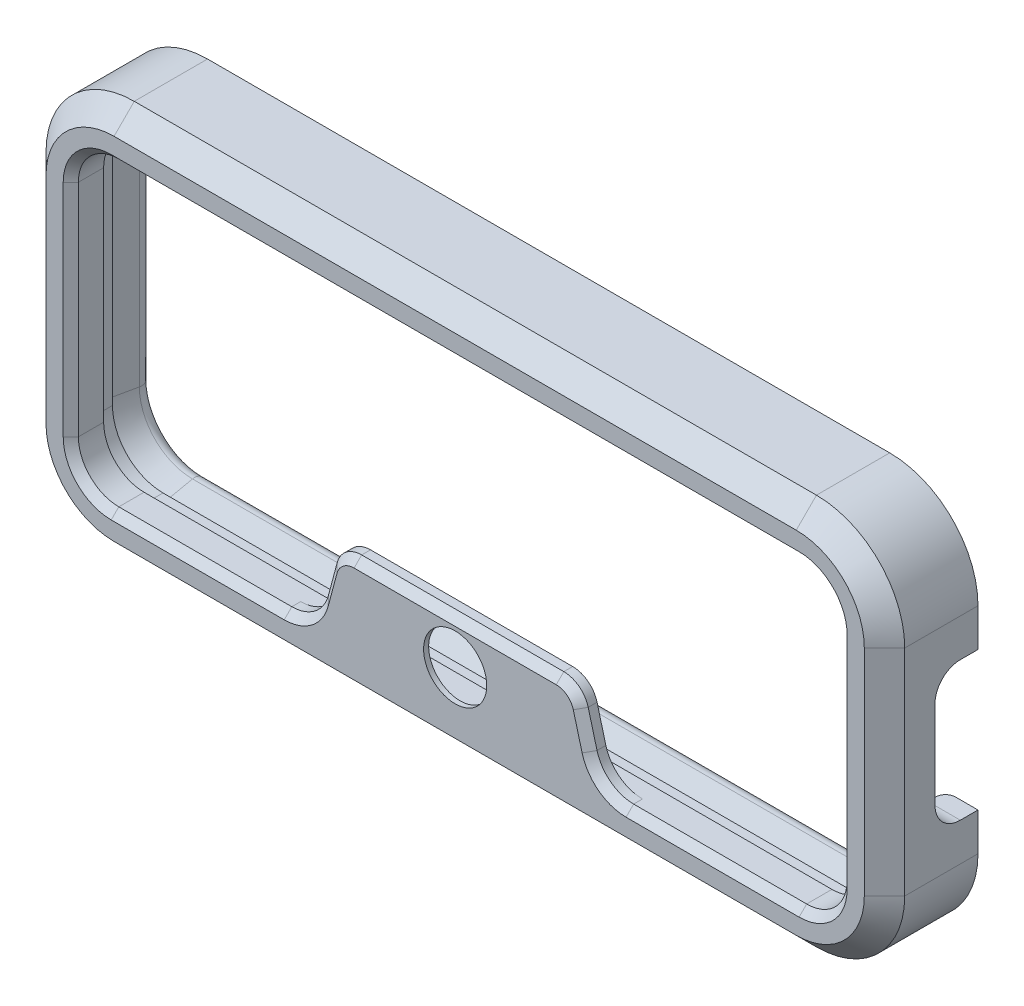
SolidWorks part; units mm, degrees
ref_plane "Ebene vorne" through (0, 0, 0) normal (0, 0, 1) x (1, 0, 0)
ref_plane "Ebene oben" through (0, 0, 0) normal (0, 1, 0) x (1, 0, 0)
ref_plane "Ebene rechts" through (0, 0, 0) normal (1, 0, 0) x (0, 0, -1)
sketch "Skizze1" plane through (0, 0, 2.3001) normal (0, 0, 1) x (1, 0, 0)
  line L0 (-27.9511, -4.5825) -> (-26.1511, -4.5825)
  line L1 (-26.1511, -4.5825) -> (-26.1511, 2.6565)
  line L2 (-26.1511, 2.6565) -> (-22.49, 2.6565)
  line L3 (-22.49, 2.6565) -> (-22.49, -4.5825)
  line L4 (-22.49, -4.5825) -> (-20.69, -4.5825)
  line L5 (-20.69, -4.5825) -> (-20.69, 2.6565)
  line L6 (-20.69, 2.6565) -> (-17.41, 2.6565)
  line L7 (-17.41, 2.6565) -> (-17.41, -4.5825)
  line L8 (-17.41, -4.5825) -> (-15.61, -4.5825)
  line L10 (-16.2652, 4.4565) -> (-27.9511, 4.4565)
  line L11 (-27.9511, 4.4565) -> (-27.9511, -4.5825)
  line L24 (-11.695, 4.4565) -> (-5.069, 4.4565)
  line L25 (-5.069, 4.4565) -> (-5.069, -4.5825)
  line L26 (-5.069, -4.5825) -> (-9.095, -4.5825)
  line L27 (-9.095, -4.5825) -> (-11.695, -4.1241)
  line L28 (-11.695, -4.1241) -> (-11.695, 0.2038)
  line L29 (-11.695, 0.2038) -> (-9.095, 0.9005)
  line L31 (-7.355, -0.8995) -> (-9.895, -0.8995)
  line L32 (-9.895, -0.8995) -> (-9.895, -2.7825)
  line L33 (-9.895, -2.7825) -> (-6.869, -2.7825)
  line L34 (-6.869, -2.7825) -> (-6.869, 2.6565)
  line L35 (-6.869, 2.6565) -> (-11.695, 2.6565)
  line L36 (-11.695, 2.6565) -> (-11.695, 4.4565)
  line L50 (1.259, 8.3935) -> (1.259, 4.4565)
  line L51 (1.259, 4.4565) -> (-1.154, 4.4565)
  line L52 (-1.154, 4.4565) -> (-1.154, 2.6565)
  line L53 (-1.154, 2.6565) -> (1.259, 2.6565)
  line L54 (1.259, 2.6565) -> (1.259, -4.5825)
  line L55 (1.259, -4.5825) -> (5.472, -4.5825)
  line L56 (5.472, -4.5825) -> (5.472, -2.7825)
  line L57 (5.472, -2.7825) -> (3.059, -2.7825)
  line L58 (3.059, -2.7825) -> (3.059, 2.6565)
  line L59 (3.059, 2.6565) -> (5.472, 2.6565)
  line L60 (5.472, 2.6565) -> (5.472, 4.4565)
  line L61 (5.472, 4.4565) -> (3.059, 4.4565)
  line L62 (3.059, 4.4565) -> (3.059, 8.3935)
  line L63 (3.059, 8.3935) -> (1.259, 8.3935)
  line L64 (-16.01, 0.6435) -> (-16.01, 1.6435) construction
  line L65 (-27.5511, 4.0565) -> (-27.5511, 3.0565) construction
  line L66 (-26.5511, -1.7695) -> (-26.5511, -0.7695) construction
  line L67 (-22.09, 1.6435) -> (-22.09, 0.6435) construction
  line L68 (-21.09, 0.6435) -> (-21.09, 1.6435) construction
  line L69 (-20.312, 3.0565) -> (-19.312, 3.0565) construction
  line L70 (-15.61, 2.6565) -> (-16.2652, 4.4565)
  line L71 (-24.138, 4.0565) -> (-25.138, 4.0565) construction
  line L72 (-27.5511, -4.1825) -> (-26.5511, -4.1825) construction
  line L73 (-17.01, 1.6435) -> (-17.01, 0.6435) construction
  line L74 (19.928, 8.2665) -> (19.928, -4.5825)
  line L75 (19.928, -4.5825) -> (21.728, -4.5825)
  line L76 (21.728, -4.5825) -> (21.728, 2.6565)
  line L77 (21.728, 2.6565) -> (25.8971, 2.6565)
  line L78 (25.8971, 2.6565) -> (25.8971, -4.5825)
  line L79 (25.8971, -4.5825) -> (27.6971, -4.5825)
  line L80 (27.6971, -4.5825) -> (27.6971, 2.6565)
  line L83 (27.0419, 4.4565) -> (21.728, 4.4565)
  line L84 (21.728, 4.4565) -> (21.728, 8.2665)
  line L85 (21.728, 8.2665) -> (19.928, 8.2665)
  line L86 (16.013, 2.6565) -> (12.057, 2.6565)
  line L87 (12.057, 2.6565) -> (11.187, 1.7865)
  line L88 (11.187, 1.7865) -> (11.187, -1.9125)
  line L89 (11.187, -1.9125) -> (12.057, -2.7825)
  line L90 (12.057, -2.7825) -> (16.013, -2.7825)
  line L91 (16.013, -2.7825) -> (16.013, -4.5825)
  line L92 (16.013, -4.5825) -> (11.155, -4.5825)
  line L93 (11.155, -4.5825) -> (9.387, -3.099)
  line L94 (9.387, -3.099) -> (9.387, 2.973)
  line L95 (9.387, 2.973) -> (11.155, 4.4565)
  line L96 (11.155, 4.4565) -> (16.013, 4.4565)
  line L97 (16.013, 4.4565) -> (16.013, 2.6565)
  line L98 (-0.754, 4.0565) -> (-0.754, 3.0565) construction
  line L99 (0.246, 4.0565) -> (-0.754, 4.0565) construction
  line L100 (1.659, 5.1995) -> (1.659, 4.1995) construction
  line L101 (2.659, 7.9935) -> (1.659, 7.9935) construction
  line L102 (2.659, 6.9935) -> (2.659, 7.9935) construction
  line L103 (5.072, 3.0565) -> (5.072, 4.0565) construction
  line L104 (4.072, 3.0565) -> (5.072, 3.0565) construction
  line L105 (2.659, 1.4055) -> (2.659, 2.4055) construction
  line L106 (5.072, -4.1825) -> (5.072, -3.1825) construction
  line L107 (5.072, -3.1825) -> (4.072, -3.1825) construction
  line L108 (1.659, -4.1825) -> (2.659, -4.1825) construction
  line L109 (9.787, 0.3735) -> (9.787, -0.6265) construction
  line L110 (10.787, -0.6265) -> (10.787, 0.3735) construction
  line L111 (-11.295, 4.0565) -> (-11.295, 3.0565) construction
  line L112 (-10.295, 4.0565) -> (-11.295, 4.0565) construction
  line L113 (14.613, 3.0565) -> (15.613, 3.0565) construction
  line L114 (15.613, 3.0565) -> (15.613, 4.0565) construction
  line L115 (13.2, 4.0565) -> (12.2, 4.0565) construction
  line L116 (12.2, -4.1825) -> (13.2, -4.1825) construction
  line L117 (20.328, -0.2615) -> (20.328, -1.2615) construction
  line L118 (21.328, -1.2615) -> (21.328, -0.2615) construction
  line L119 (22.741, 3.0565) -> (23.741, 3.0565) construction
  line L120 (26.2971, 1.7705) -> (26.2971, 0.7705) construction
  line L121 (27.2971, 0.7705) -> (27.2971, 1.7705) construction
  line L122 (23.741, 4.0565) -> (22.741, 4.0565) construction
  line L123 (21.328, 7.8665) -> (20.328, 7.8665) construction
  line L124 (21.328, 6.8665) -> (21.328, 7.8665) construction
  line L125 (27.6971, 2.6565) -> (27.0419, 4.4565)
  line L126 (20.328, -4.1825) -> (21.328, -4.1825) construction
  line L127 (-15.61, -4.5825) -> (-15.61, 2.6565)
  line L129 (-11.295, 3.0565) -> (-10.295, 3.0565) construction
  line L130 (-11.295, -0.1345) -> (-11.295, -1.1345) construction
  line L131 (-8.882, -4.1825) -> (-7.882, -4.1825) construction
  line L132 (-5.469, 3.0565) -> (-5.469, 4.0565) construction
  line L134 (-6.469, 1.6435) -> (-6.469, 0.6435) construction
  line L135 (-7.882, -3.1825) -> (-8.882, -3.1825) construction
  line L136 (-10.295, -1.1345) -> (-10.295, -0.1345) construction
  line L137 (-9.095, 0.9005) -> (-7.355, 0.9005)
  line L138 (-7.355, 0.9005) -> (-7.355, -0.8995)
  line L140 (-7.755, 0.5005) -> (-8.755, 0.5005) construction
  line L141 (-4.469, 4.8565) -> (-12.095, 4.8565)
  line L142 (-4.469, 4.8565) -> (-4.469, -5.1825)
  line L143 (-4.469, -5.1825) -> (-12.095, -5.1825)
  line L144 (-12.095, 4.8565) -> (-12.095, -5.1825)
  line L145 (-7.755, -0.4995) -> (-7.755, 0.5005) construction
  line L146 (-8.755, -0.4995) -> (-7.755, -0.4995) construction
  line L147 (-15.9151, 4.9565) -> (-28.4511, 4.9565)
  line L148 (-28.4511, 4.9565) -> (-28.4511, -5.0825)
  line L149 (-28.4511, -5.0825) -> (-25.6511, -5.0825)
  line L150 (-25.6511, -5.0825) -> (-25.6511, 2.1565)
  line L151 (-25.6511, 2.1565) -> (-22.99, 2.1565)
  line L152 (-22.99, 2.1565) -> (-22.99, -5.0825)
  line L153 (-22.99, -5.0825) -> (-20.19, -5.0825)
  line L154 (-20.19, -5.0825) -> (-20.19, 2.1565)
  line L155 (-20.19, 2.1565) -> (-17.91, 2.1565)
  line L156 (-17.91, 2.1565) -> (-17.91, -5.0825)
  line L157 (-17.91, -5.0825) -> (-15.11, -5.0825)
  line L158 (-15.11, -5.0825) -> (-15.11, 2.7447)
  line L159 (-15.11, 2.7447) -> (-15.9151, 4.9565)
  line L160 (5.972, 4.9565) -> (3.559, 4.9565)
  line L161 (3.559, 4.9565) -> (3.559, 8.8935)
  line L162 (3.559, 8.8935) -> (0.759, 8.8935)
  line L163 (0.759, 8.8935) -> (0.759, 4.9565)
  line L164 (0.759, 4.9565) -> (-1.654, 4.9565)
  line L165 (-1.654, 4.9565) -> (-1.654, 2.1565)
  line L166 (-1.654, 2.1565) -> (0.759, 2.1565)
  line L167 (0.759, 2.1565) -> (0.759, -5.0825)
  line L168 (0.759, -5.0825) -> (5.972, -5.0825)
  line L169 (5.972, -5.0825) -> (5.972, -2.2825)
  line L170 (5.972, -2.2825) -> (3.559, -2.2825)
  line L171 (3.559, -2.2825) -> (3.559, 2.1565)
  line L172 (3.559, 2.1565) -> (5.972, 2.1565)
  line L173 (5.972, 2.1565) -> (5.972, 4.9565)
  line L174 (10.973, 4.9565) -> (16.513, 4.9565)
  line L175 (16.513, 4.9565) -> (16.513, 2.1565)
  line L176 (16.513, 2.1565) -> (12.2641, 2.1565)
  line L177 (12.2641, 2.1565) -> (11.687, 1.5794)
  line L178 (11.687, 1.5794) -> (11.687, -1.7054)
  line L179 (11.687, -1.7054) -> (12.2641, -2.2825)
  line L180 (12.2641, -2.2825) -> (16.513, -2.2825)
  line L181 (16.513, -2.2825) -> (16.513, -5.0825)
  line L182 (16.513, -5.0825) -> (10.973, -5.0825)
  line L183 (10.973, -5.0825) -> (8.887, -3.3322)
  line L184 (8.887, -3.3322) -> (8.887, 3.2062)
  line L185 (8.887, 3.2062) -> (10.973, 4.9565)
  line L186 (27.322, 4.8565) -> (22.128, 4.8565)
  line L187 (22.128, 4.8565) -> (22.128, 8.6665)
  line L188 (22.128, 8.6665) -> (19.528, 8.6665)
  line L189 (19.528, 8.6665) -> (19.528, -4.9825)
  line L190 (19.528, -4.9825) -> (22.128, -4.9825)
  line L191 (22.128, -4.9825) -> (22.128, 2.2565)
  line L192 (22.128, 2.2565) -> (25.4971, 2.2565)
  line L193 (25.4971, 2.2565) -> (25.4971, -4.9825)
  line L194 (25.4971, -4.9825) -> (28.0971, -4.9825)
  line L195 (28.0971, -4.9825) -> (28.0971, 2.727)
  line L196 (28.0971, 2.727) -> (27.322, 4.8565)
  dimension "D1" = 0.4
  dimension "D2" = 0.4
  dimension "D3" = 0.4
  dimension "D4" = 0.4
  dimension "D5" = 0.4
  dimension "D7" = 0.4
  dimension "D8" = 0.4
  dimension "D9" = 0.4
  dimension "D10" = 0.4
  dimension "D11" = 0.4
  dimension "D12" = 0.4
  dimension "D13" = 0.4
  dimension "D14" = 0.4
  dimension "D15" = 0.4
  dimension "D16" = 0.4
  dimension "D17" = 0.4
  dimension "D18" = 0.4
  dimension "D19" = 0.4
  dimension "D20" = 0.4
  dimension "D21" = 0.4
  dimension "D22" = 0.4
  dimension "D23" = 0.4
  dimension "D24" = 0.4
  dimension "D25" = 0.4
  dimension "D26" = 0.4
  dimension "D27" = 130
  dimension "D28" = 135
  dimension "D29" = 0.4
  dimension "D30" = 0.4
  dimension "D31" = 0.4
  dimension "D32" = 0.4
  dimension "D33" = 0.4
  dimension "D34" = 0.4
  dimension "D35" = 0.4
  dimension "D36" = 0.4
  dimension "D37" = 0.4
  dimension "D38" = 0.4
  dimension "D39" = 20
  dimension "D40" = 0.4
  dimension "D6" = 0.4
  dimension "D41" = 200
  dimension "D42" = 0.4
  dimension "D43" = 0.4
  dimension "D44" = 0.4
  dimension "D45" = 0.4
  dimension "D46" = 0.4
  dimension "D47" = 0.4
  dimension "D48" = 0.4
  dimension "D49" = 0.4
  dimension "D50" = 0.4
  dimension "D51" = 105
  dimension "D52" = 0.4
  dimension "D53" = 0.4
  dimension "D54" = 0.4
  dimension "D55" = 2.6
  dimension "D56" = 0.4
  dimension "D58" = 0.6
  dimension "D59" = 0.4
  dimension "D57" = 10
  dimension "D64" = 2.6
  dimension "D65" = 0.6
  dimension "D60" = 0.5
  dimension "D61" = 0.5
  dimension "D62" = 0.5
  dimension "D63" = 0.4
extrude "Aufsatz-Linear austragen1" add sketch "Skizze1" along normal blind 1.5
sketch "Skizze2" plane through (0, 0, 3.8001) normal (0, 0, 1) x (1, 0, 0)
  line L0 (30.9874, 8.5) -> (30.9874, -8.5) construction
  line L1 (27.0001, -12.4873) -> (-27.0001, -12.4873) construction
  line L2 (-30.9874, -8.5) -> (-30.9874, 8.5) construction
  line L3 (-27.0001, 12.4873) -> (27.0001, 12.4873) construction
  line L4 (30.9874, 8.5) -> (30.9874, -8.5) construction
  line L5 (27.0001, -12.4873) -> (-27.0001, -12.4873) construction
  line L6 (-30.9874, -8.5) -> (-30.9874, 8.5) construction
  line L7 (-27.0001, 12.4873) -> (27.0001, 12.4873) construction
  line L8 (-27.0001, 15.4873) -> (27.0001, 15.4873)
  line L9 (33.9874, 8.5) -> (33.9874, -8.5)
  line L10 (27.0001, -15.4873) -> (-27.0001, -15.4873)
  line L11 (-33.9874, -8.5) -> (-33.9874, 8.5)
  arc A0 (30.9874, 8.5) -> (27.0001, 12.4873) centre (27.0001, 8.5) ccw construction
  arc A1 (27.0001, -12.4873) -> (30.9874, -8.5) centre (27.0001, -8.5) ccw construction
  arc A2 (-30.9874, -8.5) -> (-27.0001, -12.4873) centre (-27.0001, -8.5) ccw construction
  arc A3 (-27.0001, 12.4873) -> (-30.9874, 8.5) centre (-27.0001, 8.5) ccw construction
  arc A4 (30.9874, 8.5) -> (27.0001, 12.4873) centre (27.0001, 8.5) ccw construction
  arc A5 (27.0001, -12.4873) -> (30.9874, -8.5) centre (27.0001, -8.5) ccw construction
  arc A6 (-30.9874, -8.5) -> (-27.0001, -12.4873) centre (-27.0001, -8.5) ccw construction
  arc A7 (-27.0001, 12.4873) -> (-30.9874, 8.5) centre (-27.0001, 8.5) ccw construction
  circle A8 centre (0, -9.017) radius 2.5
  arc A9 (0.7218, -9.017) -> (-0.7218, -9.017) centre (0, -9.017) ccw construction
  arc A10 (0.7218, -9.017) -> (-0.7218, -9.017) centre (0, -9.017) ccw construction
  arc A11 (33.9874, 8.5) -> (27.0001, 15.4873) centre (27.0001, 8.5) ccw
  arc A12 (27.0001, -15.4873) -> (33.9874, -8.5) centre (27.0001, -8.5) ccw
  arc A13 (-33.9874, -8.5) -> (-27.0001, -15.4873) centre (-27.0001, -8.5) ccw
  arc A14 (-27.0001, 15.4873) -> (-33.9874, 8.5) centre (-27.0001, 8.5) ccw
  dimension "D1" = 5
  dimension "D2" = 3
extrude "Aufsatz-Linear austragen2" add sketch "Skizze2" along normal blind 0.4
sketch "Skizze3" plane through (0, 0, 3.8001) normal (0, 0, -1) x (-1, 0, 0)
  line L12 (-27.225, 11.925) -> (27.225, 11.925)
  line L13 (-27.225, -12.725) -> (27.225, -12.725)
  line L14 (-31.225, -8.725) -> (-31.225, 8.725)
  line L15 (-27.225, 12.725) -> (27.225, 12.725)
  line L16 (31.225, -8.725) -> (31.225, 8.725)
  line L17 (-31.225, -12.725) -> (31.225, 12.725) construction
  line L18 (-31.225, 12.725) -> (31.225, -12.725) construction
  line L19 (30.425, -8.725) -> (30.425, 8.725)
  line L20 (-27.225, -11.925) -> (27.225, -11.925)
  line L21 (-30.425, -8.725) -> (-30.425, 8.725)
  arc A12 (27.225, 12.725) -> (31.225, 8.725) centre (27.225, 8.725) cw
  arc A13 (27.225, -12.725) -> (31.225, -8.725) centre (27.225, -8.725) ccw
  arc A14 (-31.225, -8.725) -> (-27.225, -12.725) centre (-27.225, -8.725) ccw
  arc A15 (-31.225, 8.725) -> (-27.225, 12.725) centre (-27.225, 8.725) cw
  arc A16 (27.225, 11.925) -> (30.425, 8.725) centre (27.225, 8.725) cw
  arc A17 (27.225, -11.925) -> (30.425, -8.725) centre (27.225, -8.725) ccw
  arc A18 (-30.425, -8.725) -> (-27.225, -11.925) centre (-27.225, -8.725) ccw
  arc A19 (-30.425, 8.725) -> (-27.225, 11.925) centre (-27.225, 8.725) cw
  point P0 (0, 0)
  dimension "D3" = 4
  dimension "D1" = 62.45
  dimension "D2" = 25.45
  dimension "D4" = 0.8
extrude "Aufsatz-Linear austragen3" add sketch "Skizze3" along normal blind 2.2
sketch "Skizze10" plane through (0, 0, 3.8001) normal (0, 0, -1) x (-1, 0, 0)
  line L0 (27.225, 12.725) -> (-27.225, 12.725) construction
  line L1 (27.225, 12.725) -> (-27.225, 12.725)
  line L4 (27.0001, 15.4873) -> (-27.0001, 15.4873)
  line L5 (-33.9874, 8.5) -> (-33.9874, -8.5)
  line L6 (-27.0001, -15.4873) -> (27.0001, -15.4873)
  line L7 (33.9874, -8.5) -> (33.9874, 8.5)
  line L8 (27.0001, 15.4873) -> (-27.0001, 15.4873)
  line L9 (-33.9874, 8.5) -> (-33.9874, -8.5)
  line L10 (-27.0001, -15.4873) -> (27.0001, -15.4873)
  line L11 (33.9874, -8.5) -> (33.9874, 8.5)
  line L14 (31.225, -8.725) -> (31.225, 8.725)
  line L15 (31.225, -8.725) -> (31.225, 8.725)
  line L16 (-27.225, -12.725) -> (27.225, -12.725)
  line L17 (-27.225, -12.725) -> (27.225, -12.725)
  line L22 (-31.225, 8.725) -> (-31.225, -8.725)
  line L23 (-31.225, 8.725) -> (-31.225, -8.725)
  line L24 (27.225, 12.725) -> (-27.225, 12.725)
  line L25 (27.225, 12.725) -> (-27.225, 12.725)
  arc A1 (27.225, -12.725) -> (31.225, -8.725) centre (27.225, -8.725) ccw
  arc A4 (33.9874, 8.5) -> (27.0001, 15.4873) centre (27.0001, 8.5) ccw
  arc A5 (-27.0001, 15.4873) -> (-33.9874, 8.5) centre (-27.0001, 8.5) ccw
  arc A6 (-33.9874, -8.5) -> (-27.0001, -15.4873) centre (-27.0001, -8.5) ccw
  arc A7 (27.0001, -15.4873) -> (33.9874, -8.5) centre (27.0001, -8.5) ccw
  arc A8 (33.9874, 8.5) -> (27.0001, 15.4873) centre (27.0001, 8.5) ccw
  arc A9 (-27.0001, 15.4873) -> (-33.9874, 8.5) centre (-27.0001, 8.5) ccw
  arc A10 (-33.9874, -8.5) -> (-27.0001, -15.4873) centre (-27.0001, -8.5) ccw
  arc A11 (27.0001, -15.4873) -> (33.9874, -8.5) centre (27.0001, -8.5) ccw
  arc A15 (27.225, -12.725) -> (31.225, -8.725) centre (27.225, -8.725) ccw
  arc A20 (-31.225, -8.725) -> (-27.225, -12.725) centre (-27.225, -8.725) ccw
  arc A21 (-31.225, -8.725) -> (-27.225, -12.725) centre (-27.225, -8.725) ccw
  arc A22 (-27.225, 12.725) -> (-31.225, 8.725) centre (-27.225, 8.725) ccw
  arc A23 (-27.225, 12.725) -> (-31.225, 8.725) centre (-27.225, 8.725) ccw
  arc A24 (31.225, 8.725) -> (27.225, 12.725) centre (27.225, 8.725) ccw
  arc A25 (31.225, 8.725) -> (27.225, 12.725) centre (27.225, 8.725) ccw
  dimension "D1" = 0
  dimension "D2" = 0
extrude "Aufsatz-Linear austragen14" add sketch "Skizze10" along normal blind 7 contours A8 L8 A9 L9 A10 L10 A11 L11 | L15 A25 L25 A23 L23 A21 L17 A15
sketch "Skizze11" plane through (0, 0, 0) normal (1, 0, 0) x (0, 0, -1)
  line L0 (3.1999, 12.725) -> (-1.6001, 12.725) construction
  line L1 (3.1999, 12.725) -> (-0.1001, 12.725)
  line L2 (-0.1001, 12.725) -> (3.1999, 12.725)
  line L3 (3.1999, 12.725) -> (-0.1001, 13.4264)
  line L4 (-0.1001, 13.4264) -> (-0.1001, 12.725)
  line L5 (-0.1001, 13.4264) -> (3.1999, 12.725)
  line L6 (3.1999, 12.725) -> (-1.6001, 12.725)
  dimension "D1" = 12
  dimension "D2" = 1.5
sketch "Skizze12" plane through (0, 0, -3.1999) normal (0, 0, -1) x (-1, 0, 0)
  line L4 (31.225, -8.725) -> (31.225, 8.725)
  line L16 (31.225, -8.725) -> (31.225, 8.725)
  line L20 (-27.225, -12.725) -> (27.225, -12.725)
  line L22 (-27.225, -12.725) -> (27.225, -12.725)
  line L24 (-31.225, 8.725) -> (-31.225, -8.725)
  line L25 (-31.225, 8.725) -> (-31.225, -8.725)
  line L26 (27.225, 12.725) -> (-27.225, 12.725)
  line L27 (27.225, 12.725) -> (-27.225, 12.725)
  arc A4 (27.225, -12.725) -> (31.225, -8.725) centre (27.225, -8.725) ccw
  arc A16 (27.225, -12.725) -> (31.225, -8.725) centre (27.225, -8.725) ccw
  arc A20 (-31.225, -8.725) -> (-27.225, -12.725) centre (-27.225, -8.725) ccw
  arc A22 (-31.225, -8.725) -> (-27.225, -12.725) centre (-27.225, -8.725) ccw
  arc A24 (-27.225, 12.725) -> (-31.225, 8.725) centre (-27.225, 8.725) ccw
  arc A25 (-27.225, 12.725) -> (-31.225, 8.725) centre (-27.225, 8.725) ccw
  arc A26 (31.225, 8.725) -> (27.225, 12.725) centre (27.225, 8.725) ccw
  arc A27 (31.225, 8.725) -> (27.225, 12.725) centre (27.225, 8.725) ccw
  dimension "D1" = 0
sketch "Skizze14" plane through (0, 0, 3.8001) normal (0, 0, -1) x (-1, 0, 0)
  line L4 (27.225, 11.925) -> (-27.225, 11.925)
  line L5 (-30.425, 8.725) -> (-30.425, -8.725)
  line L6 (-27.225, -11.925) -> (27.225, -11.925)
  line L7 (30.425, -8.725) -> (30.425, 8.725)
  line L8 (27.225, 11.925) -> (-27.225, 11.925)
  line L9 (-30.425, 8.725) -> (-30.425, -8.725)
  line L10 (-27.225, -11.925) -> (27.225, -11.925)
  line L11 (30.425, -8.725) -> (30.425, 8.725)
  line L12 (4.469, -5.1825) -> (12.095, -5.1825)
  line L13 (4.469, 4.8565) -> (4.469, -5.1825)
  line L14 (12.095, 4.8565) -> (4.469, 4.8565)
  line L15 (12.095, -5.1825) -> (12.095, 4.8565)
  line L16 (4.469, -5.1825) -> (12.095, -5.1825)
  line L17 (4.469, 4.8565) -> (4.469, -5.1825)
  line L18 (12.095, 4.8565) -> (4.469, 4.8565)
  line L19 (12.095, -5.1825) -> (12.095, 4.8565)
  line L21 (15.9151, 4.9565) -> (15.11, 2.7447)
  line L22 (28.4511, 4.9565) -> (15.9151, 4.9565)
  line L23 (28.4511, -5.0825) -> (28.4511, 4.9565)
  line L24 (25.6511, -5.0825) -> (28.4511, -5.0825)
  line L25 (25.6511, 2.1565) -> (25.6511, -5.0825)
  line L26 (22.99, 2.1565) -> (25.6511, 2.1565)
  line L27 (22.99, -5.0825) -> (22.99, 2.1565)
  line L28 (20.19, -5.0825) -> (22.99, -5.0825)
  line L29 (20.19, 2.1565) -> (20.19, -5.0825)
  line L30 (17.91, 2.1565) -> (20.19, 2.1565)
  line L31 (17.91, -5.0825) -> (17.91, 2.1565)
  line L32 (15.11, -5.0825) -> (17.91, -5.0825)
  line L33 (15.11, 2.7447) -> (15.11, -5.0825)
  line L34 (15.9151, 4.9565) -> (15.11, 2.7447)
  line L35 (28.4511, 4.9565) -> (15.9151, 4.9565)
  line L36 (28.4511, -5.0825) -> (28.4511, 4.9565)
  line L37 (25.6511, -5.0825) -> (28.4511, -5.0825)
  line L38 (25.6511, 2.1565) -> (25.6511, -5.0825)
  line L39 (22.99, 2.1565) -> (25.6511, 2.1565)
  line L40 (22.99, -5.0825) -> (22.99, 2.1565)
  line L41 (20.19, -5.0825) -> (22.99, -5.0825)
  line L42 (20.19, 2.1565) -> (20.19, -5.0825)
  line L43 (17.91, 2.1565) -> (20.19, 2.1565)
  line L44 (17.91, -5.0825) -> (17.91, 2.1565)
  line L45 (15.11, -5.0825) -> (17.91, -5.0825)
  line L46 (15.11, 2.7447) -> (15.11, -5.0825)
  line L53 (-27.322, 4.8565) -> (-28.0971, 2.727)
  line L54 (-8.887, 3.2062) -> (-10.973, 4.9565)
  line L55 (-8.887, -3.3322) -> (-8.887, 3.2062)
  line L56 (-5.972, 4.9565) -> (-5.972, 2.1565)
  line L57 (-3.559, 4.9565) -> (-5.972, 4.9565)
  line L58 (-3.559, 8.8935) -> (-3.559, 4.9565)
  line L59 (-0.759, 8.8935) -> (-3.559, 8.8935)
  line L60 (-0.759, 4.9565) -> (-0.759, 8.8935)
  line L61 (1.654, 4.9565) -> (-0.759, 4.9565)
  line L62 (1.654, 2.1565) -> (1.654, 4.9565)
  line L63 (-0.759, 2.1565) -> (1.654, 2.1565)
  line L64 (-0.759, -5.0825) -> (-0.759, 2.1565)
  line L65 (-5.972, -5.0825) -> (-0.759, -5.0825)
  line L66 (-5.972, -2.2825) -> (-5.972, -5.0825)
  line L67 (-3.559, -2.2825) -> (-5.972, -2.2825)
  line L68 (-3.559, 2.1565) -> (-3.559, -2.2825)
  line L69 (-5.972, 2.1565) -> (-3.559, 2.1565)
  line L70 (-5.972, 4.9565) -> (-5.972, 2.1565)
  line L71 (-3.559, 4.9565) -> (-5.972, 4.9565)
  line L72 (-3.559, 8.8935) -> (-3.559, 4.9565)
  line L73 (-0.759, 8.8935) -> (-3.559, 8.8935)
  line L74 (-0.759, 4.9565) -> (-0.759, 8.8935)
  line L75 (1.654, 4.9565) -> (-0.759, 4.9565)
  line L76 (1.654, 2.1565) -> (1.654, 4.9565)
  line L77 (-0.759, 2.1565) -> (1.654, 2.1565)
  line L78 (-0.759, -5.0825) -> (-0.759, 2.1565)
  line L79 (-5.972, -5.0825) -> (-0.759, -5.0825)
  line L80 (-5.972, -2.2825) -> (-5.972, -5.0825)
  line L81 (-3.559, -2.2825) -> (-5.972, -2.2825)
  line L82 (-3.559, 2.1565) -> (-3.559, -2.2825)
  line L83 (-5.972, 2.1565) -> (-3.559, 2.1565)
  line L84 (-10.973, -5.0825) -> (-8.887, -3.3322)
  line L85 (-16.513, -5.0825) -> (-10.973, -5.0825)
  line L86 (-16.513, -2.2825) -> (-16.513, -5.0825)
  line L87 (-12.2641, -2.2825) -> (-16.513, -2.2825)
  line L88 (-11.687, -1.7054) -> (-12.2641, -2.2825)
  line L89 (-11.687, 1.5794) -> (-11.687, -1.7054)
  line L90 (-12.2641, 2.1565) -> (-11.687, 1.5794)
  line L91 (-16.513, 2.1565) -> (-12.2641, 2.1565)
  line L92 (-16.513, 4.9565) -> (-16.513, 2.1565)
  line L93 (-10.973, 4.9565) -> (-16.513, 4.9565)
  line L94 (-8.887, 3.2062) -> (-10.973, 4.9565)
  line L95 (-8.887, -3.3322) -> (-8.887, 3.2062)
  line L96 (-10.973, -5.0825) -> (-8.887, -3.3322)
  line L97 (-16.513, -5.0825) -> (-10.973, -5.0825)
  line L98 (-16.513, -2.2825) -> (-16.513, -5.0825)
  line L99 (-12.2641, -2.2825) -> (-16.513, -2.2825)
  line L100 (-11.687, -1.7054) -> (-12.2641, -2.2825)
  line L101 (-11.687, 1.5794) -> (-11.687, -1.7054)
  line L102 (-12.2641, 2.1565) -> (-11.687, 1.5794)
  line L103 (-16.513, 2.1565) -> (-12.2641, 2.1565)
  line L104 (-16.513, 4.9565) -> (-16.513, 2.1565)
  line L105 (-10.973, 4.9565) -> (-16.513, 4.9565)
  line L106 (-22.128, 4.8565) -> (-27.322, 4.8565)
  line L107 (-22.128, 8.6665) -> (-22.128, 4.8565)
  line L108 (-19.528, 8.6665) -> (-22.128, 8.6665)
  line L109 (-19.528, -4.9825) -> (-19.528, 8.6665)
  line L110 (-22.128, -4.9825) -> (-19.528, -4.9825)
  line L111 (-22.128, 2.2565) -> (-22.128, -4.9825)
  line L112 (-25.4971, 2.2565) -> (-22.128, 2.2565)
  line L113 (-25.4971, -4.9825) -> (-25.4971, 2.2565)
  line L114 (-28.0971, -4.9825) -> (-25.4971, -4.9825)
  line L115 (-28.0971, 2.727) -> (-28.0971, -4.9825)
  line L116 (-27.322, 4.8565) -> (-28.0971, 2.727)
  line L117 (-22.128, 4.8565) -> (-27.322, 4.8565)
  line L118 (-22.128, 8.6665) -> (-22.128, 4.8565)
  line L119 (-19.528, 8.6665) -> (-22.128, 8.6665)
  line L120 (-19.528, -4.9825) -> (-19.528, 8.6665)
  line L121 (-22.128, -4.9825) -> (-19.528, -4.9825)
  line L122 (-22.128, 2.2565) -> (-22.128, -4.9825)
  line L123 (-25.4971, 2.2565) -> (-22.128, 2.2565)
  line L124 (-25.4971, -4.9825) -> (-25.4971, 2.2565)
  line L125 (-28.0971, -4.9825) -> (-25.4971, -4.9825)
  line L126 (-28.0971, 2.727) -> (-28.0971, -4.9825)
  circle A1 centre (0, -9.017) radius 2.5
  circle A2 centre (0, -9.017) radius 2.5
  arc A4 (30.425, 8.725) -> (27.225, 11.925) centre (27.225, 8.725) ccw
  arc A5 (-27.225, 11.925) -> (-30.425, 8.725) centre (-27.225, 8.725) ccw
  arc A6 (-30.425, -8.725) -> (-27.225, -11.925) centre (-27.225, -8.725) ccw
  arc A7 (27.225, -11.925) -> (30.425, -8.725) centre (27.225, -8.725) ccw
  arc A8 (30.425, 8.725) -> (27.225, 11.925) centre (27.225, 8.725) ccw
  arc A9 (-27.225, 11.925) -> (-30.425, 8.725) centre (-27.225, 8.725) ccw
  arc A10 (-30.425, -8.725) -> (-27.225, -11.925) centre (-27.225, -8.725) ccw
  arc A11 (27.225, -11.925) -> (30.425, -8.725) centre (27.225, -8.725) ccw
  dimension "D1" = 0
  dimension "D2" = 0
  dimension "D3" = 0
  dimension "D4" = 0
  dimension "D5" = 0
  dimension "D6" = 0
  dimension "D7" = 0
extrude "Aufsatz-Linear austragen15" add sketch "Skizze14" along normal blind 0.9
sweep "Schnitt-Austragung1" cut profiles "Skizze11" path "Skizze12"
fillet "Verrundung1" radius 0.8 9 edges at (-30.0534, -11.5534, -3.1999) (0, -12.725, -3.1999) (30.0534, -11.5534, -3.1999) (31.225, 0, -3.1999) (30.0534, 11.5534, -3.1999) (13.6125, 12.725, -3.1999) (-13.6125, 12.725, -3.1999) (-30.0534, 11.5534, -3.1999) (-31.225, 0, -3.1999)
sketch "Skizze13" plane through (33.9874, 0, 0) normal (1, 0, 0) x (0, 0, -1)
  line L0 (3.1999, 8.5) -> (3.1999, -8.5) construction
  line L1 (1.7999, -5.5) -> (3.9999, -5.5)
  line L2 (-0.2001, -3.5) -> (-0.2001, 3.5)
  line L3 (1.7999, 5.5) -> (3.9999, 5.5)
  line L4 (5.9999, -3.5) -> (5.9999, 3.5)
  line L5 (-0.2001, -5.5) -> (5.9999, 5.5) construction
  line L6 (-0.2001, 5.5) -> (5.9999, -5.5) construction
  arc A0 (3.9999, -5.5) -> (5.9999, -3.5) centre (3.9999, -3.5) ccw
  arc A1 (1.7999, -5.5) -> (-0.2001, -3.5) centre (1.7999, -3.5) cw
  arc A2 (1.7999, 5.5) -> (-0.2001, 3.5) centre (1.7999, 3.5) ccw
  arc A3 (5.9999, 3.5) -> (3.9999, 5.5) centre (3.9999, 3.5) ccw
  point P0 (2.8999, 0)
  point P18 (0, 0)
  dimension "D1" = 2
  dimension "D2" = 11
  dimension "D3" = 6.2
  dimension "D4" = 0.3
extrude "Schnitt-Linear austragen1" cut sketch "Skizze13" against normal blind 5 contours L2 A2 L3 A3 L4 A0 L1 A1
sketch "Skizze15" plane through (0, 0, 2.9001) normal (0, 0, -1) x (-1, 0, 0)
  line L0 (-5, -9.017) -> (5, -9.017) construction
  line L1 (-5, -6.109) -> (5, -6.109)
  line L2 (-5, -11.925) -> (5, -11.925)
  line L3 (-27.225, -11.925) -> (27.225, -11.925) construction
  arc A0 (-5, -6.109) -> (-5, -11.925) centre (-5, -9.017) ccw
  arc A1 (5, -11.925) -> (5, -6.109) centre (5, -9.017) ccw
  point P2 (0, -9.017)
  dimension "D1" = 10
extrude "Schnitt-Linear austragen2" cut sketch "Skizze15" against normal blind 0.9
chamfer "Fase1" distance 1.6 angle 45 8 edges at (-31.9408, -13.4408, 4.2001) (0, -15.4873, 4.2001) (-33.9874, 0, 4.2001) (31.9408, -13.4408, 4.2001) (-31.9408, 13.4408, 4.2001) (33.9874, 0, 4.2001) (0, 15.4873, 4.2001) (31.9408, 13.4408, 4.2001)
sketch "Skizze16" plane through (0, 0, 3.8001) normal (0, 0, -1) x (-1, 0, 0)
  line L0 (26.1511, -4.5825) -> (27.9511, -4.5825) construction
  line L1 (27.9511, -4.5825) -> (27.9511, 4.4565) construction
  line L2 (27.9511, 4.4565) -> (16.2652, 4.4565) construction
  line L3 (16.2652, 4.4565) -> (15.61, 2.6565) construction
  line L4 (15.61, 2.6565) -> (15.61, -4.5825) construction
  line L5 (15.61, -4.5825) -> (17.41, -4.5825) construction
  line L6 (17.41, -4.5825) -> (17.41, 2.6565) construction
  line L7 (17.41, 2.6565) -> (20.69, 2.6565) construction
  line L8 (20.69, 2.6565) -> (20.69, -4.5825) construction
  line L9 (20.69, -4.5825) -> (22.49, -4.5825) construction
  line L10 (22.49, -4.5825) -> (22.49, 2.6565) construction
  line L11 (22.49, 2.6565) -> (26.1511, 2.6565) construction
  line L12 (26.1511, 2.6565) -> (26.1511, -4.5825) construction
  line L13 (7.355, 0.9005) -> (7.355, -0.8995) construction
  line L14 (7.355, -0.8995) -> (9.895, -0.8995) construction
  line L15 (9.895, -0.8995) -> (9.895, -2.7825) construction
  line L16 (9.895, -2.7825) -> (6.869, -2.7825) construction
  line L17 (6.869, -2.7825) -> (6.869, 2.6565) construction
  line L18 (6.869, 2.6565) -> (11.695, 2.6565) construction
  line L19 (11.695, 2.6565) -> (11.695, 4.4565) construction
  line L20 (11.695, 4.4565) -> (5.069, 4.4565) construction
  line L21 (5.069, 4.4565) -> (5.069, -4.5825) construction
  line L22 (5.069, -4.5825) -> (9.095, -4.5825) construction
  line L23 (9.095, -4.5825) -> (11.695, -4.1241) construction
  line L24 (11.695, -4.1241) -> (11.695, 0.2038) construction
  line L25 (11.695, 0.2038) -> (9.095, 0.9005) construction
  line L26 (9.095, 0.9005) -> (7.355, 0.9005) construction
  line L27 (-1.259, 4.4565) -> (-1.259, 8.3935) construction
  line L28 (-1.259, 8.3935) -> (-3.059, 8.3935) construction
  line L29 (-3.059, 8.3935) -> (-3.059, 4.4565) construction
  line L30 (-3.059, 4.4565) -> (-5.472, 4.4565) construction
  line L31 (-5.472, 4.4565) -> (-5.472, 2.6565) construction
  line L32 (-5.472, 2.6565) -> (-3.059, 2.6565) construction
  line L33 (-3.059, 2.6565) -> (-3.059, -2.7825) construction
  line L34 (-3.059, -2.7825) -> (-5.472, -2.7825) construction
  line L35 (-5.472, -2.7825) -> (-5.472, -4.5825) construction
  line L36 (-5.472, -4.5825) -> (-1.259, -4.5825) construction
  line L37 (-1.259, -4.5825) -> (-1.259, 2.6565) construction
  line L38 (-1.259, 2.6565) -> (1.154, 2.6565) construction
  line L39 (1.154, 2.6565) -> (1.154, 4.4565) construction
  line L40 (1.154, 4.4565) -> (-1.259, 4.4565) construction
  line L41 (-11.155, 4.4565) -> (-16.013, 4.4565) construction
  line L42 (-16.013, 4.4565) -> (-16.013, 2.6565) construction
  line L43 (-16.013, 2.6565) -> (-12.057, 2.6565) construction
  line L44 (-12.057, 2.6565) -> (-11.187, 1.7865) construction
  line L45 (-11.187, 1.7865) -> (-11.187, -1.9125) construction
  line L46 (-11.187, -1.9125) -> (-12.057, -2.7825) construction
  line L47 (-12.057, -2.7825) -> (-16.013, -2.7825) construction
  line L48 (-16.013, -2.7825) -> (-16.013, -4.5825) construction
  line L49 (-16.013, -4.5825) -> (-11.155, -4.5825) construction
  line L50 (-11.155, -4.5825) -> (-9.387, -3.099) construction
  line L51 (-9.387, -3.099) -> (-9.387, 2.973) construction
  line L52 (-9.387, 2.973) -> (-11.155, 4.4565) construction
  line L53 (-19.928, -4.5825) -> (-19.928, 8.2665) construction
  line L54 (-19.928, 8.2665) -> (-21.728, 8.2665) construction
  line L55 (-21.728, 8.2665) -> (-21.728, 4.4565) construction
  line L56 (-21.728, 4.4565) -> (-27.0419, 4.4565) construction
  line L57 (-27.0419, 4.4565) -> (-27.6971, 2.6565) construction
  line L58 (-27.6971, 2.6565) -> (-27.6971, -4.5825) construction
  line L59 (-27.6971, -4.5825) -> (-25.8971, -4.5825) construction
  line L60 (-25.8971, -4.5825) -> (-25.8971, 2.6565) construction
  line L61 (-25.8971, 2.6565) -> (-21.728, 2.6565) construction
  line L62 (-21.728, 2.6565) -> (-21.728, -4.5825) construction
  line L63 (-21.728, -4.5825) -> (-19.928, -4.5825) construction
  line L64 (26.1511, -4.5825) -> (27.9511, -4.5825)
  line L65 (27.9511, -4.5825) -> (27.9511, 4.4565)
  line L66 (27.9511, 4.4565) -> (16.2652, 4.4565)
  line L67 (16.2652, 4.4565) -> (15.61, 2.6565)
  line L68 (15.61, 2.6565) -> (15.61, -4.5825)
  line L69 (15.61, -4.5825) -> (17.41, -4.5825)
  line L70 (17.41, -4.5825) -> (17.41, 2.6565)
  line L71 (17.41, 2.6565) -> (20.69, 2.6565)
  line L72 (20.69, 2.6565) -> (20.69, -4.5825)
  line L73 (20.69, -4.5825) -> (22.49, -4.5825)
  line L74 (22.49, -4.5825) -> (22.49, 2.6565)
  line L75 (22.49, 2.6565) -> (26.1511, 2.6565)
  line L76 (26.1511, 2.6565) -> (26.1511, -4.5825)
  line L77 (7.355, 0.9005) -> (7.355, -0.8995)
  line L78 (7.355, -0.8995) -> (9.895, -0.8995)
  line L79 (9.895, -0.8995) -> (9.895, -2.7825)
  line L80 (9.895, -2.7825) -> (6.869, -2.7825)
  line L81 (6.869, -2.7825) -> (6.869, 2.6565)
  line L82 (6.869, 2.6565) -> (11.695, 2.6565)
  line L83 (11.695, 2.6565) -> (11.695, 4.4565)
  line L84 (11.695, 4.4565) -> (5.069, 4.4565)
  line L85 (5.069, 4.4565) -> (5.069, -4.5825)
  line L86 (5.069, -4.5825) -> (9.095, -4.5825)
  line L87 (9.095, -4.5825) -> (11.695, -4.1241)
  line L88 (11.695, -4.1241) -> (11.695, 0.2038)
  line L89 (11.695, 0.2038) -> (9.095, 0.9005)
  line L90 (9.095, 0.9005) -> (7.355, 0.9005)
  line L91 (-1.259, 4.4565) -> (-1.259, 8.3935)
  line L92 (-1.259, 8.3935) -> (-3.059, 8.3935)
  line L93 (-3.059, 8.3935) -> (-3.059, 4.4565)
  line L94 (-3.059, 4.4565) -> (-5.472, 4.4565)
  line L95 (-5.472, 4.4565) -> (-5.472, 2.6565)
  line L96 (-5.472, 2.6565) -> (-3.059, 2.6565)
  line L97 (-3.059, 2.6565) -> (-3.059, -2.7825)
  line L98 (-3.059, -2.7825) -> (-5.472, -2.7825)
  line L99 (-5.472, -2.7825) -> (-5.472, -4.5825)
  line L100 (-5.472, -4.5825) -> (-1.259, -4.5825)
  line L101 (-1.259, -4.5825) -> (-1.259, 2.6565)
  line L102 (-1.259, 2.6565) -> (1.154, 2.6565)
  line L103 (1.154, 2.6565) -> (1.154, 4.4565)
  line L104 (1.154, 4.4565) -> (-1.259, 4.4565)
  line L105 (-11.155, 4.4565) -> (-16.013, 4.4565)
  line L106 (-16.013, 4.4565) -> (-16.013, 2.6565)
  line L107 (-16.013, 2.6565) -> (-12.057, 2.6565)
  line L108 (-12.057, 2.6565) -> (-11.187, 1.7865)
  line L109 (-11.187, 1.7865) -> (-11.187, -1.9125)
  line L110 (-11.187, -1.9125) -> (-12.057, -2.7825)
  line L111 (-12.057, -2.7825) -> (-16.013, -2.7825)
  line L112 (-16.013, -2.7825) -> (-16.013, -4.5825)
  line L113 (-16.013, -4.5825) -> (-11.155, -4.5825)
  line L114 (-11.155, -4.5825) -> (-9.387, -3.099)
  line L115 (-9.387, -3.099) -> (-9.387, 2.973)
  line L116 (-9.387, 2.973) -> (-11.155, 4.4565)
  line L117 (-19.928, -4.5825) -> (-19.928, 8.2665)
  line L118 (-19.928, 8.2665) -> (-21.728, 8.2665)
  line L119 (-21.728, 8.2665) -> (-21.728, 4.4565)
  line L120 (-21.728, 4.4565) -> (-27.0419, 4.4565)
  line L121 (-27.0419, 4.4565) -> (-27.6971, 2.6565)
  line L122 (-27.6971, 2.6565) -> (-27.6971, -4.5825)
  line L123 (-27.6971, -4.5825) -> (-25.8971, -4.5825)
  line L124 (-25.8971, -4.5825) -> (-25.8971, 2.6565)
  line L125 (-25.8971, 2.6565) -> (-21.728, 2.6565)
  line L126 (-21.728, 2.6565) -> (-21.728, -4.5825)
  line L127 (-21.728, -4.5825) -> (-19.928, -4.5825)
extrude "Cut_Letters_optional" [suppressed] cut sketch "Skizze16" against normal through all contours L117 L118 L119 L120 L121 L122 L123 L124 L125 L126 L127 | L105 L106 L107 L108 L109 L110 L111 L112 L113 L114 L115 L116 | L91 L92 L93 L94 L95 L96 L97 L98 L99 L100 L101 L102 L103 L104 | L77 L78 L79 L80 L81 L82 L83 L84 L85 L86 L87 L88 L89 L90 | L64 L65 L66 L67 L68 L69 L70 L71 L72 L73 L74 L75 L76
sketch "Skizze17" plane through (0, 0, 4.2001) normal (0, 0, 1) x (1, 0, 0)
  circle A1 centre (0, -9.017) radius 2.5
  circle A2 centre (0, -9.017) radius 2.5
  circle A3 centre (0, -9.017) radius 2.5
  circle A4 centre (0, -9.017) radius 2.5
  circle A5 centre (0, -9.017) radius 2.5
  circle A6 centre (0, -9.017) radius 2.5
  circle A7 centre (0, -9.017) radius 2.5
  circle A8 centre (0, -9.017) radius 2.5
  circle A9 centre (0, -9.017) radius 2.5
  circle A10 centre (0, -9.017) radius 2.5
  dimension "D1" = 0
  dimension "D2" = 0
  dimension "D3" = 0
  dimension "D4" = 0
  dimension "D5" = 0
extrude "Letters_single" [suppressed] add sketch "Skizze17" against normal blind 0.3 separate body
sketch "Skizze18" plane through (0, 0, 4.2001) normal (0, 0, 1) x (1, 0, 0)
  line L0 (-27.225, 11.925) -> (27.225, 11.925) construction
  line L1 (-27.225, 11.925) -> (27.225, 11.925)
  line L2 (-5, -6.109) -> (5, -6.109) construction
  line L3 (-30.425, -8.725) -> (-30.425, 8.725) construction
  line L4 (30.425, 8.725) -> (30.425, -8.725) construction
  line L5 (-5, -6.109) -> (5, -6.109) construction
  line L6 (-30.425, -8.725) -> (-30.425, 8.725)
  line L7 (30.425, 8.725) -> (30.425, -8.725)
  line L8 (-27.225, -11.925) -> (-13.529, -11.925)
  line L9 (27.225, -11.925) -> (13.529, -11.925)
  line L10 (9.9319, -7.0914) -> (10.6312, -9.7015)
  line L11 (8, -5.609) -> (-8, -5.609)
  line L12 (-9.9319, -7.0914) -> (-10.6312, -9.7015)
  arc A0 (-5, -6.109) -> (-5, -11.925) centre (-5, -9.017) ccw construction
  arc A1 (5, -11.925) -> (5, -6.109) centre (5, -9.017) ccw construction
  arc A2 (27.225, -11.925) -> (30.425, -8.725) centre (27.225, -8.725) ccw construction
  arc A3 (-30.425, -8.725) -> (-27.225, -11.925) centre (-27.225, -8.725) ccw construction
  arc A4 (-27.225, 11.925) -> (-30.425, 8.725) centre (-27.225, 8.725) ccw construction
  arc A5 (30.425, 8.725) -> (27.225, 11.925) centre (27.225, 8.725) ccw construction
  arc A6 (-5, -6.109) -> (-5, -11.925) centre (-5, -9.017) ccw construction
  arc A7 (5, -11.925) -> (5, -6.109) centre (5, -9.017) ccw construction
  arc A8 (27.225, -11.925) -> (30.425, -8.725) centre (27.225, -8.725) ccw
  arc A9 (-30.425, -8.725) -> (-27.225, -11.925) centre (-27.225, -8.725) ccw
  arc A10 (-27.225, 11.925) -> (-30.425, 8.725) centre (-27.225, 8.725) ccw
  arc A11 (30.425, 8.725) -> (27.225, 11.925) centre (27.225, 8.725) ccw
  arc A12 (-13.529, -11.925) -> (-10.6312, -9.7015) centre (-13.529, -8.925) ccw
  arc A13 (-9.9319, -7.0914) -> (-8, -5.609) centre (-8, -7.609) cw
  arc A14 (8, -5.609) -> (9.9319, -7.0914) centre (8, -7.609) cw
  arc A15 (13.529, -11.925) -> (10.6312, -9.7015) centre (13.529, -8.925) cw
  point P30 (0, -5.609)
  point P31 (0, -6.109)
  dimension "D4" = 3
  dimension "D5" = 2
  dimension "D1" = 1
  dimension "D2" = 30
  dimension "D3" = 16
extrude "Schnitt-Linear austragen4" cut sketch "Skizze18" against normal through all
chamfer "Fase2" distance 0.6 angle 45 16 edges at (0, -5.609, 4.2001) (9.2175, -6.0223, 4.2001) (-9.2175, -6.0223, 4.2001) (10.2815, -8.3964, 4.2001) (-10.2815, -8.3964, 4.2001) (11.7027, -11.3051, 4.2001) (-11.7027, -11.3051, 4.2001) (20.377, -11.925, 4.2001) (-20.377, -11.925, 4.2001) (29.4877, -10.9877, 4.2001) (-29.4877, -10.9877, 4.2001) (30.425, 0, 4.2001) (-30.425, 0, 4.2001) (29.4877, 10.9877, 4.2001) (-29.4877, 10.9877, 4.2001) (0, 11.925, 4.2001)
equation "\"D2@Skizze1\"=\"D1@Skizze1\""
equation "\"D3@Skizze1\"=\"D1@Skizze1\""
equation "\"D4@Skizze1\"=\"D1@Skizze1\""
equation "\"D5@Skizze1\"=\"D1@Skizze1\""
equation "\"D7@Skizze1\"=\"D1@Skizze1\""
equation "\"D8@Skizze1\"=\"D1@Skizze1\""
equation "\"D9@Skizze1\"=\"D1@Skizze1\""
equation "\"D11@Skizze1\"=\"D10@Skizze1\""
equation "\"D12@Skizze1\"=\"D10@Skizze1\""
equation "\"D13@Skizze1\"=\"D10@Skizze1\""
equation "\"D14@Skizze1\"=\"D10@Skizze1\""
equation "\"D15@Skizze1\"=\"D10@Skizze1\""
equation "\"D16@Skizze1\"=\"D10@Skizze1\""
equation "\"D17@Skizze1\"=\"D10@Skizze1\""
equation "\"D18@Skizze1\"=\"D10@Skizze1\""
equation "\"D20@Skizze1\"=\"D10@Skizze1\""
equation "\"D22@Skizze1\"=\"D21@Skizze1\""
equation "\"D23@Skizze1\"=\"D21@Skizze1\""
equation "\"D24@Skizze1\"=\"D21@Skizze1\""
equation "\"D25@Skizze1\"=\"D21@Skizze1\""
equation "\"D26@Skizze1\"=\"D21@Skizze1\""
equation "\"D33@Skizze1\"=\"D31@Skizze1\""
equation "\"D34@Skizze1\"=\"D31@Skizze1\""
equation "\"D35@Skizze1\"=\"D31@Skizze1\""
equation "\"D37@Skizze1\"=\"D31@Skizze1\""
equation "\"D38@Skizze1\"=\"D31@Skizze1\""
equation "\"D40@Skizze1\"=\"D31@Skizze1\""
equation "\"D32@Skizze1\"=\"D31@Skizze1\""
equation "\"D6@Skizze1\"=\"D1@Skizze1\""
equation "\"D43@Skizze1\"=\"D42@Skizze1\""
equation "\"D44@Skizze1\"=\"D42@Skizze1\""
equation "\"D45@Skizze1\"=\"D44@Skizze1\""
equation "\"D46@Skizze1\"=\"D42@Skizze1\""
equation "\"D47@Skizze1\"=\"D42@Skizze1\""
equation "\"D48@Skizze1\"=\"D42@Skizze1\""
equation "\"D49@Skizze1\"=\"D42@Skizze1\""
equation "\"D50@Skizze1\"=\"D42@Skizze1\""
equation "\"D54@Skizze1\"=\"D42@Skizze1\""
equation "\"D19@Skizze1\"=\"D10@Skizze1\""
